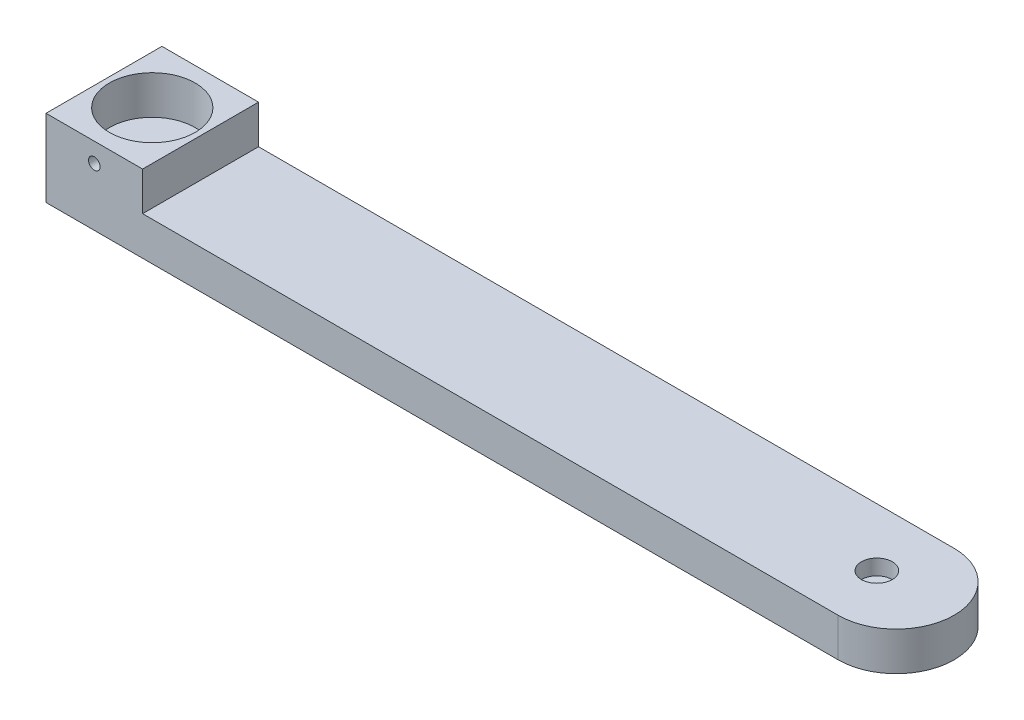
SolidWorks part; units mm, degrees
ref_plane "Front Plane" through (0, 0, 0) normal (0, 0, 1) x (1, 0, 0)
ref_plane "Top Plane" through (0, 0, 0) normal (0, 1, 0) x (1, 0, 0)
ref_plane "Right Plane" through (0, 0, 0) normal (1, 0, 0) x (0, 0, -1)
sketch "Sketch1" plane through (0, 0, 0) normal (0, 1, 0) x (1, 0, 0)
  line L1 (-110, -15) -> (110, -15)
  line L2 (-110, -15) -> (-110, 15)
  line L3 (-110, 15) -> (110, 15)
  line L4 (110, -15) -> (110, 15)
  line L5 (-110, -15) -> (110, 15) construction
  line L6 (-110, 15) -> (110, -15) construction
  circle A0 centre (95, 0) radius 15
  point P0 (0, 0)
  point P8 (95, 3.9869)
  dimension "D3" = 30
  dimension "D1" = 220
  dimension "D2" = 30
extrude "Boss-Extrude1" add sketch "Sketch1" along normal blind 10 contours A0 L3 L2 L1 | A0 region at (-13.3615, 0, 0) region at (95, 0, 0)
sketch "Sketch2" plane through (0, 10, 0) normal (0, 1, 0) x (1, 0, 0)
  line L0 (-5.5, 0) -> (5.5, 0) construction
  line L2 (-85, -15) -> (-110, -15)
  line L3 (-85, -15) -> (-85, 15)
  line L4 (-85, 15) -> (-110, 15)
  line L5 (-110, -15) -> (-110, 15)
  line L6 (-85, -15) -> (-110, 15) construction
  line L7 (-85, 15) -> (-110, -15) construction
  circle A1 centre (-97.5, 0) radius 11.1
  point P0 (0, 0)
  dimension "D1" = 25
  dimension "D2" = 22.2
extrude "Boss-Extrude3" add sketch "Sketch2" along normal blind 10 contours L3 A1 region at (-97.5, 10, 14.6095)
sketch "Sketch4" plane through (0, 10, 0) normal (0, 1, 0) x (1, 0, 0)
  line L0 (-5.5, 0) -> (5.5, 0) construction
  circle A0 centre (90, 0) radius 4
  arc A1 (95, -15) -> (95, 15) centre (95, 0) ccw construction
  dimension "D1" = 8
  dimension "D2" = 5
sketch "Sketch6" plane through (0, 0, 15) normal (0, 0, 1) x (1, 0, 0)
  line L0 (-85, 10) -> (-110, 10) construction
  line L1 (-110, 20) -> (-110, 0) construction
  line L2 (-97.5, 20) -> (-97.5, 10) construction
  circle A0 centre (-97.5, 15) radius 1.5
  point P7 (0, 0)
  point P11 (0, 0)
  dimension "D1" = 3
extrude "Cut-Extrude2" cut sketch "Sketch6" against normal blind 10
extrude "Cut-Extrude3" cut sketch "Sketch4" against normal blind 4 from surface starting at face at (8.75, 10, 0)
sketch "Sketch7" plane through (0, 6, 0) normal (0, 1, 0) x (1, 0, 0)
  circle A0 centre (90, 0) radius 1.5
  dimension "D1" = 3
extrude "Cut-Extrude4" cut sketch "Sketch7" against normal blind 14
